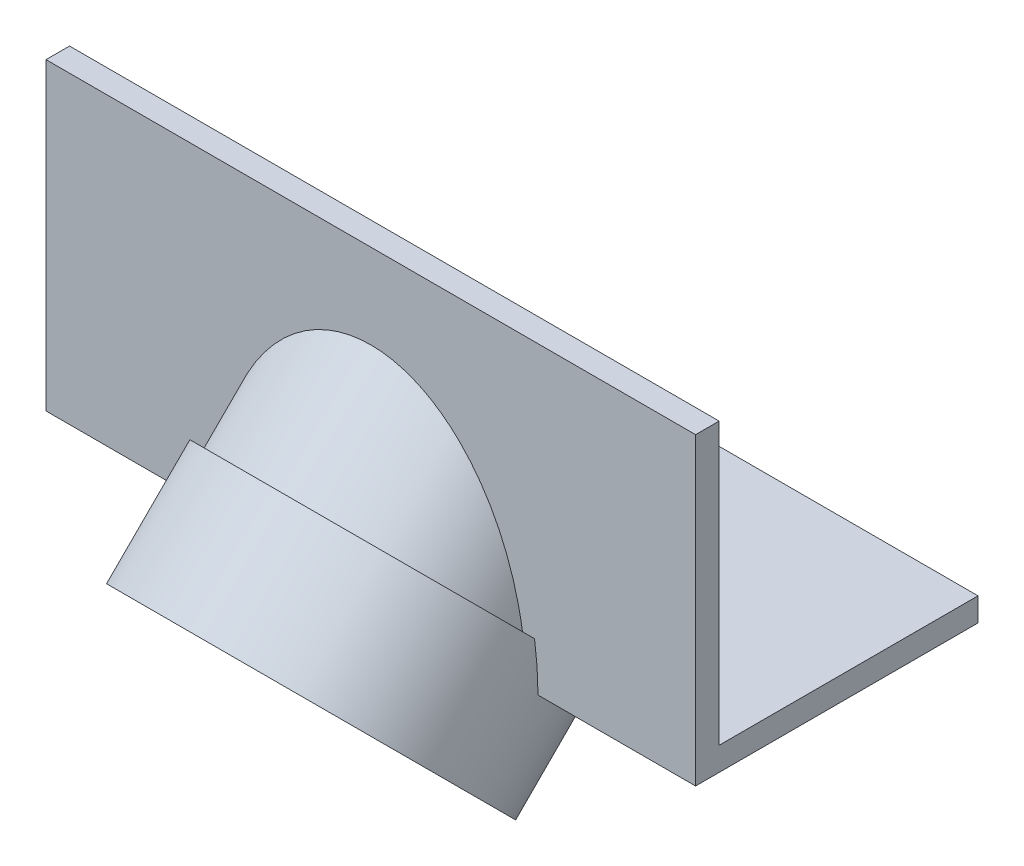
SolidWorks part; units mm, degrees
ref_plane "Front Plane" through (0, 0, 0) normal (0, 0, 1) x (1, 0, 0)
ref_plane "Top Plane" through (0, 0, 0) normal (0, 1, 0) x (1, 0, 0)
ref_plane "Right Plane" through (0, 0, 0) normal (1, 0, 0) x (0, 0, -1)
sketch "Sketch1" plane through (0, 0, 0) normal (1, 0, 0) x (0, 0, -1)
  line L0 (-11.0588, 7.6359) -> (-11.0588, -5.2941)
  line L1 (-11.0588, -5.2941) -> (0.9412, -5.2941)
  line L2 (0.9412, -5.2941) -> (0.9412, -4.2941)
  line L3 (0.9412, -4.2941) -> (-10.0588, -4.2941)
  line L4 (-10.0588, -4.2941) -> (-10.0588, 7.6359)
  line L5 (-10.0588, 7.6359) -> (-11.0588, 7.6359)
  dimension "D1" = 1
  dimension "D2" = 1
  dimension "D3" = 12
  dimension "D4" = 12.93
extrude "Boss-Extrude1" add sketch "Sketch1" along normal blind 27.6022
ref_axis "Axis2" through (27.6022, -4.2941, 10.0588) along (-1, 0, 0)
ref_plane "Plane2" through (0, -7.1765, 7.1765) normal (0, 0.7071, -0.7071) x (-1, 0, 0)
sketch "Sketch3" plane through (0, -7.1765, 7.1765) normal (0, 0.7071, -0.7071) x (-1, 0, 0)
  line L0 (-13.8011, 12.512) -> (-13.8011, -3.7019) construction
  line L1 (-27.6022, 12.512) -> (0, 12.512) construction
  line L2 (-27.6022, -3.7019) -> (0, -3.7019) construction
  line L3 (0, 4.0763) -> (-27.6022, 4.0763) construction
  circle A0 centre (-13.8011, 4.0763) radius 5.1
  circle A1 centre (-13.8011, 4.0763) radius 7.1
  dimension "D1" = 10.2
  dimension "D2" = 2
extrude "Boss-Extrude2" add sketch "Sketch3" against normal blind 5
sketch "Sketch4" plane through (0, -7.1765, 7.1765) normal (0, 0.7071, -0.7071) x (-1, 0, 0)
  circle A0 centre (-13.8011, 4.0763) radius 5.6
  circle A1 centre (-13.8011, 4.0763) radius 6.6
  dimension "D1" = 11.2
  dimension "D2" = 1
extrude "Boss-Extrude3" add sketch "Sketch4" along normal blind 7.62
sketch "Sketch5" plane through (0, -1.7883, 1.7883) normal (0, 0.7071, -0.7071) x (1, 0, 0)
  circle A0 centre (13.8011, -4.0763) radius 5.6
extrude "Cut-Extrude1" cut sketch "Sketch5" against normal blind 7.62
sketch "Sketch6" plane through (0, -1.7883, 1.7883) normal (0, 0.7071, -0.7071) x (1, 0, 0)
  circle A0 centre (13.8011, -4.0763) radius 5.1
extrude "Cut-Extrude2" cut sketch "Sketch6" against normal blind 19.05
